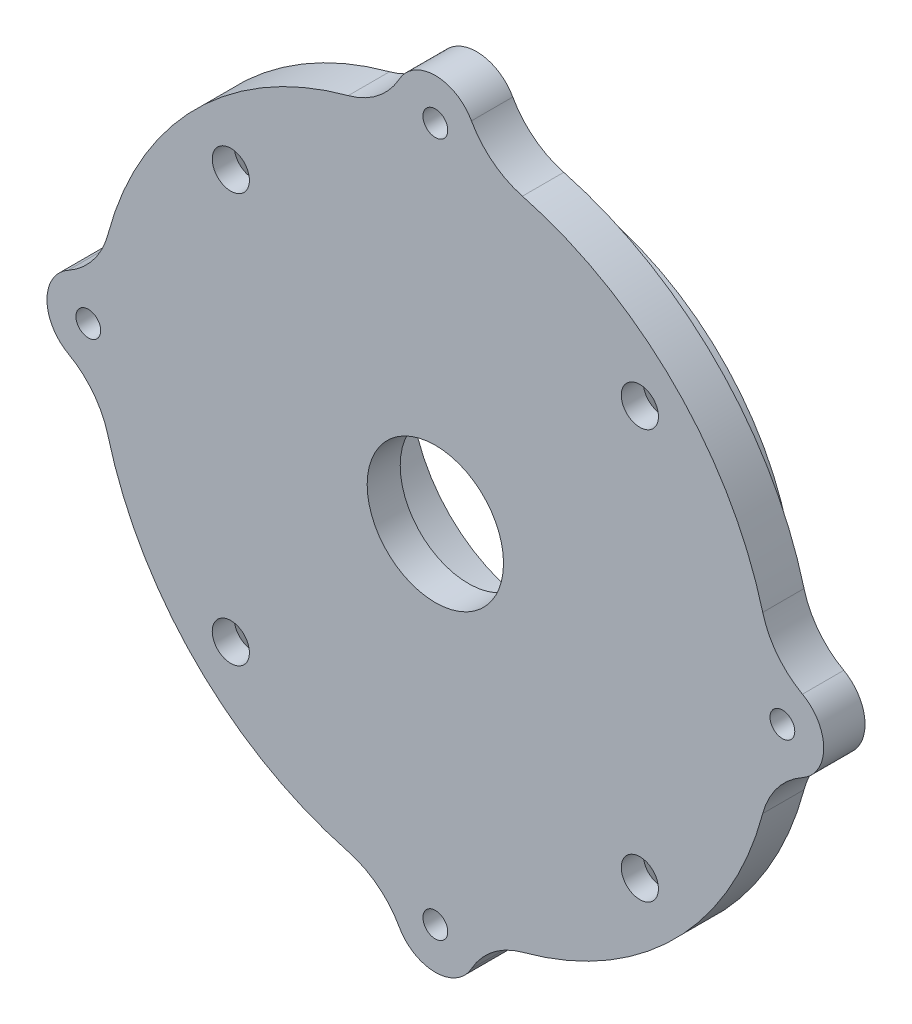
SolidWorks part; units mm, degrees
ref_plane "Ön Düzlem" through (0, 0, 0) normal (0, 0, 1) x (1, 0, 0)
ref_plane "Üst Düzlem" through (0, 0, 0) normal (0, 1, 0) x (1, 0, 0)
ref_plane "Sağ Düzlem" through (0, 0, 0) normal (1, 0, 0) x (0, 0, -1)
sketch "Çizim1" plane through (0, 0, 0) normal (0, 0, 1) x (1, 0, 0)
  circle A0 centre (0, 0) radius 16.25
  circle A1 centre (0, 0) radius 22.5
  circle A2 centre (0, 0) radius 30.3
  circle A3 centre (0, 0) radius 28
  dimension "D1" = 32.5
  dimension "D2" = 45
  dimension "D3" = 60.6
  dimension "D4" = 56
extrude "Yükseklik-Ekstrüzyon1" add sketch "Çizim1" along normal blind 8.25 contours A1 A0 | A2 A3 region at (-21.8636, 0, 0) region at (-29.443, 0, 0)
sketch "Çizim2" plane through (0, 0, 8.25) normal (0, 0, 1) x (1, 0, 0)
  circle A0 centre (-24.75, 24.75) radius 2
  circle A1 centre (24.75, 24.75) radius 2
  circle A2 centre (24.75, -24.75) radius 2
  circle A3 centre (-24.75, -24.75) radius 2
  arc A6 (-10.5408, 39.6218) -> (-39.6218, 10.5408) centre (0, 0) ccw
  circle A7 centre (0, 42) radius 1.5
  arc A8 (4.3706, 44.4286) -> (-4.3706, 44.4286) centre (0, 42) ccw
  arc A9 (-4.3706, 44.4286) -> (-10.5408, 39.6218) centre (-13.1118, 49.2857) cw
  arc A10 (4.3706, 44.4286) -> (10.5408, 39.6218) centre (13.1118, 49.2857) ccw
  arc A11 (44.4286, 4.3706) -> (39.6218, 10.5408) centre (49.2857, 13.1118) cw
  arc A12 (44.4286, -4.3706) -> (44.4286, 4.3706) centre (42, 0) ccw
  circle A13 centre (42, 0) radius 1.5
  arc A14 (44.4286, -4.3706) -> (39.6218, -10.5408) centre (49.2857, -13.1118) ccw
  arc A15 (4.3706, -44.4286) -> (10.5408, -39.6218) centre (13.1118, -49.2857) cw
  arc A16 (-4.3706, -44.4286) -> (4.3706, -44.4286) centre (0, -42) ccw
  circle A17 centre (0, -42) radius 1.5
  arc A18 (-4.3706, -44.4286) -> (-10.5408, -39.6218) centre (-13.1118, -49.2857) ccw
  arc A19 (-44.4286, -4.3706) -> (-39.6218, -10.5408) centre (-49.2857, -13.1118) cw
  arc A20 (-44.4286, 4.3706) -> (-44.4286, -4.3706) centre (-42, 0) ccw
  circle A21 centre (-42, 0) radius 1.5
  arc A22 (-44.4286, 4.3706) -> (-39.6218, 10.5408) centre (-49.2857, 13.1118) ccw
  arc A23 (-39.6218, -10.5408) -> (-10.5408, -39.6218) centre (0, 0) ccw
  arc A24 (10.5408, -39.6218) -> (39.6218, -10.5408) centre (0, 0) ccw
  arc A25 (39.6218, 10.5408) -> (10.5408, 39.6218) centre (0, 0) ccw
  circle A26 centre (0, 0) radius 8.25
  point P0 (0, 0)
  point P17 (0, 0)
  point P48 (0, 0)
  dimension "D3" = 4
  dimension "D4" = 24.75
  dimension "D5" = 24.75
  dimension "D1" = 82
  dimension "D2" = 42
  dimension "D7" = 10
  dimension "D8" = 3
  dimension "D9" = 10
  dimension "D10" = 10
  dimension "D12" = 16.5
  dimension "D6" = 4
  dimension "D11" = 4
extrude "Yükseklik-Ekstrüzyon2" add sketch "Çizim2" along normal blind 5
hole_wizard "M4 Altıgen Alyan Havşa Başlı Vida İçin Havşa2" positions "3B Çizim1" profile "Çizim5" countersink size "M4" standard "DIN" end condition through all
sketch3d "3B Çizim1"
  line L0 (24.75, 24.75, 13.25) -> (24.75, 24.75, 8.25) construction
  line L1 (-24.75, 24.75, 13.25) -> (-24.75, 24.75, 8.25) construction
  line L2 (-24.75, -24.75, 13.25) -> (-24.75, -24.75, 8.25) construction
  line L3 (24.75, -24.75, 13.25) -> (24.75, -24.75, 8.25) construction
  point P0 (24.75, 24.75, 8.25)
  point P4 (-24.75, 24.75, 8.25)
  point P8 (-24.75, -24.75, 8.25)
  point P12 (24.75, -24.75, 8.25)
sketch "Çizim5" plane through (24.75, 24.75, 8.25) normal (1, 0, 0) x (0, 1, 0)
  line L0 (0, 0) -> (0, 5)
  line L1 (0, 5) -> (2.25, 5)
  line L2 (2.25, 5) -> (2.25, 2.34)
  line L3 (2.25, 2.34) -> (4.59, 0)
  line L5 (4.59, 0) -> (0, 0)
  line L6 (-2.25, 2.34) -> (-4.59, 0) construction
  line L11 (0, -6.35) -> (0, 107.95) construction
  dimension "Thru Hole Dia." = 4.5
  dimension "Thru Hole Depth" = 5
  dimension "Near C'Sink Dia." = 9.18
  dimension "Near C'Sink Angle" = 90
sketch "Çizim7" plane through (0, 0, 8.25) normal (0, 0, -1) x (-1, 0, 0)
  circle A0 centre (0, 0) radius 16.25 construction
  circle A1 centre (0, 0) radius 16.25
extrude "Kes-Ekstrüzyon2" cut sketch "Çizim7" against normal blind 1
